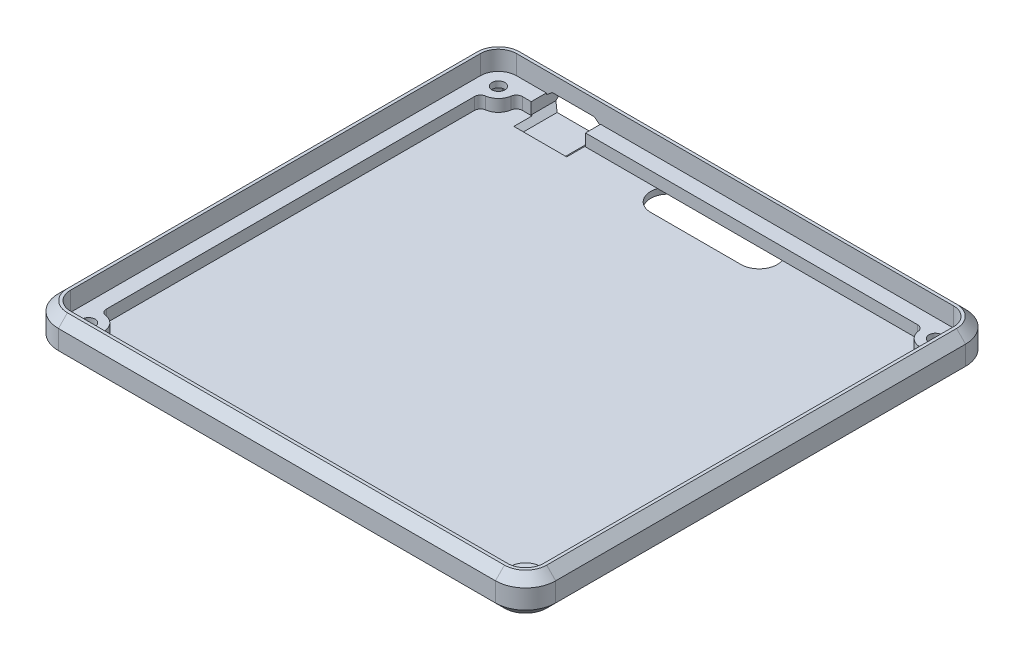
SolidWorks part; units mm, degrees
material "ABS"
ref_plane "Front Plane" through (0, 0, 0) normal (0, 0, 1) x (1, 0, 0)
ref_plane "Top Plane" through (0, 0, 0) normal (0, 1, 0) x (1, 0, 0)
ref_plane "Right Plane" through (0, 0, 0) normal (1, 0, 0) x (0, 0, -1)
sketch "Sketch2" plane through (0, 0, 0) normal (0, 1, 0) x (1, 0, 0)
  line L1 (-72.5, 74) -> (72.5, 74)
  line L2 (-78.5, 68) -> (-78.5, -68)
  line L3 (-72.5, -74) -> (72.5, -74)
  line L4 (78.5, 68) -> (78.5, -68)
  line L5 (-78.5, 74) -> (78.5, -74) construction
  line L6 (-78.5, -74) -> (78.5, 74) construction
  arc A0 (-78.5, -68) -> (-72.5, -74) centre (-72.5, -68) ccw
  arc A1 (-72.5, 74) -> (-78.5, 68) centre (-72.5, 68) ccw
  arc A2 (72.5, 74) -> (78.5, 68) centre (72.5, 68) cw
  arc A3 (72.5, -74) -> (78.5, -68) centre (72.5, -68) ccw
  point P0 (0, 0)
  dimension "D3" = 6
  dimension "D1" = 157
  dimension "D2" = 148
extrude "Boss-Extrude2" add sketch "Sketch2" along normal blind 2
sketch "Sketch3" plane through (0, 2, 0) normal (0, 1, 0) x (1, 0, 0)
  line L0 (-72.5, -74) -> (72.5, -74) construction
  line L1 (78.5, -68) -> (78.5, 68) construction
  line L2 (72.5, 74) -> (-72.5, 74) construction
  line L3 (-78.5, 68) -> (-78.5, -68) construction
  line L4 (-72.5, -74) -> (72.5, -74)
  line L5 (78.5, -68) -> (78.5, 68)
  line L6 (72.5, 74) -> (-72.5, 74)
  line L7 (-78.5, 68) -> (-78.5, -68)
  line L8 (0, -80.5945) -> (0, 82.9206) construction
  line L9 (9.041, 0) -> (-113.0904, 0) construction
  line L10 (-82.5, 68) -> (-82.5, -68)
  line L11 (-72.5, -78) -> (72.5, -78)
  line L12 (82.5, -68) -> (82.5, 68)
  line L13 (72.5, 78) -> (-72.5, 78)
  line L14 (-73.5, 63) -> (-73.5, -63)
  line L15 (-67.5, -69) -> (67.5, -69)
  line L16 (73.5, -63) -> (73.5, 63)
  line L17 (67.5, 69) -> (-67.5, 69)
  line L18 (-73.5, 63) -> (-72.5, 63)
  line L19 (-67.5, 69) -> (-67.5, 68)
  line L20 (-73.5, 68) -> (-73.5, -68) construction
  line L21 (72.5, 69) -> (-72.5, 69) construction
  line L22 (67.5, 69) -> (67.5, 68)
  line L23 (73.5, 63) -> (72.5, 63)
  line L24 (67.5, -69) -> (67.5, -68)
  line L25 (73.5, -63) -> (72.5, -63)
  line L26 (-67.5, -69) -> (-67.5, -68)
  line L27 (-73.5, -63) -> (-72.5, -63)
  line L28 (-72.5, -69) -> (72.5, -69) construction
  line L29 (73.5, -68) -> (73.5, 68) construction
  arc A0 (-78.5, -68) -> (-72.5, -74) centre (-72.5, -68) ccw construction
  arc A1 (72.5, -74) -> (78.5, -68) centre (72.5, -68) ccw construction
  arc A2 (78.5, 68) -> (72.5, 74) centre (72.5, 68) ccw construction
  arc A3 (-72.5, 74) -> (-78.5, 68) centre (-72.5, 68) ccw construction
  arc A4 (-78.5, -68) -> (-72.5, -74) centre (-72.5, -68) ccw
  arc A5 (72.5, -74) -> (78.5, -68) centre (72.5, -68) ccw
  arc A6 (78.5, 68) -> (72.5, 74) centre (72.5, 68) ccw
  arc A7 (-72.5, 74) -> (-78.5, 68) centre (-72.5, 68) ccw
  circle A9 centre (-72.5, -68) radius 2.15
  circle A10 centre (72.5, -68) radius 2.15
  circle A11 centre (72.5, 68) radius 2.15
  circle A12 centre (-72.5, 68) radius 2.15
  arc A13 (-82.5, -68) -> (-72.5, -78) centre (-72.5, -68) ccw
  arc A14 (72.5, -78) -> (82.5, -68) centre (72.5, -68) ccw
  arc A15 (82.5, 68) -> (72.5, 78) centre (72.5, 68) ccw
  arc A16 (-72.5, 78) -> (-82.5, 68) centre (-72.5, 68) ccw
  arc A21 (-72.5, 63) -> (-67.5, 68) centre (-72.5, 68) ccw
  arc A22 (72.5, 63) -> (67.5, 68) centre (72.5, 68) cw
  arc A23 (-72.5, 69) -> (-73.5, 68) centre (-72.5, 68) ccw construction
  arc A24 (72.5, -63) -> (67.5, -68) centre (72.5, -68) ccw
  arc A25 (-72.5, -63) -> (-67.5, -68) centre (-72.5, -68) cw
  arc A26 (-73.5, -68) -> (-72.5, -69) centre (-72.5, -68) ccw construction
  arc A27 (72.5, -69) -> (73.5, -68) centre (72.5, -68) ccw construction
  arc A28 (73.5, 68) -> (72.5, 69) centre (72.5, 68) ccw construction
  arc M10 (-78.5, -68) -> (-72.5, -74) centre (-72.5, -68) ccw
  line M11 (-72.5, -74) -> (72.5, -74)
  arc M12 (72.5, -74) -> (78.5, -68) centre (72.5, -68) ccw
  line M13 (78.5, -68) -> (78.5, 68)
  arc M14 (78.5, 68) -> (72.5, 74) centre (72.5, 68) ccw
  line M15 (72.5, 74) -> (-72.5, 74)
  arc M16 (-72.5, 74) -> (-78.5, 68) centre (-72.5, 68) ccw
  line M17 (-78.5, 68) -> (-78.5, -68)
  dimension "D1" = 68
  dimension "D2" = 4.3
  dimension "D3" = 72.5
  dimension "D4" = 4
  dimension "D6" = 1
  dimension "D7" = 5
  dimension "D8" = 1
  dimension "D9" = 5
  dimension "D5" = 5
extrude "Boss-Extrude3" add sketch "Sketch3" along normal blind 4 and the other way blind 2 contours L13 A16 L10 A13 L11 A14 L12 A15 M10 M17 M16 M15 M14 M13 M12 M11 | L17 L16 L15 L14 M17 M10 M11 M12 M13 M14 M15 M16 region at (-75.217, 2, 70.717) region at (-77.9654, 2, -73.4654)
sketch "Sketch8" plane through (0, 6, 0) normal (0, 1, 0) x (1, 0, 0)
  line L0 (-72.5, -78) -> (72.5, -78) construction
  line L1 (82.5, -68) -> (82.5, 68) construction
  line L2 (72.5, 78) -> (-72.5, 78) construction
  line L3 (-82.5, 68) -> (-82.5, -68) construction
  line L4 (78.5, -68) -> (78.5, 68)
  line L5 (72.5, 74) -> (-72.5, 74)
  line L6 (-78.5, 68) -> (-78.5, -68)
  line L7 (-72.5, -74) -> (72.5, -74)
  line L8 (78.5, -68) -> (78.5, 68)
  line L9 (72.5, 74) -> (-72.5, 74)
  line L10 (-78.5, 68) -> (-78.5, -68)
  line L11 (-72.5, -74) -> (72.5, -74)
  line L12 (-72.5, -78) -> (72.5, -78)
  line L13 (82.5, -68) -> (82.5, 68)
  line L14 (72.5, 78) -> (-72.5, 78)
  line L15 (-82.5, 68) -> (-82.5, -68)
  line L16 (-77.5, 68) -> (-77.5, -68)
  line L17 (-72.5, -73) -> (72.5, -73)
  line L18 (77.5, -68) -> (77.5, 68)
  line L19 (72.5, 73) -> (-72.5, 73)
  arc A0 (-82.5, -68) -> (-72.5, -78) centre (-72.5, -68) ccw construction
  arc A1 (72.5, -78) -> (82.5, -68) centre (72.5, -68) ccw construction
  arc A2 (82.5, 68) -> (72.5, 78) centre (72.5, 68) ccw construction
  arc A3 (-72.5, 78) -> (-82.5, 68) centre (-72.5, 68) ccw construction
  arc A4 (78.5, 68) -> (72.5, 74) centre (72.5, 68) ccw
  arc A5 (-72.5, 74) -> (-78.5, 68) centre (-72.5, 68) ccw
  arc A6 (-78.5, -68) -> (-72.5, -74) centre (-72.5, -68) ccw
  arc A7 (72.5, -74) -> (78.5, -68) centre (72.5, -68) ccw
  arc A8 (78.5, 68) -> (72.5, 74) centre (72.5, 68) ccw
  arc A9 (-72.5, 74) -> (-78.5, 68) centre (-72.5, 68) ccw
  arc A10 (-78.5, -68) -> (-72.5, -74) centre (-72.5, -68) ccw
  arc A11 (72.5, -74) -> (78.5, -68) centre (72.5, -68) ccw
  arc A12 (-82.5, -68) -> (-72.5, -78) centre (-72.5, -68) ccw
  arc A13 (72.5, -78) -> (82.5, -68) centre (72.5, -68) ccw
  arc A14 (82.5, 68) -> (72.5, 78) centre (72.5, 68) ccw
  arc A15 (-72.5, 78) -> (-82.5, 68) centre (-72.5, 68) ccw
  arc A16 (-77.5, -68) -> (-72.5, -73) centre (-72.5, -68) ccw
  arc A17 (72.5, -73) -> (77.5, -68) centre (72.5, -68) ccw
  arc A18 (77.5, 68) -> (72.5, 73) centre (72.5, 68) ccw
  arc A19 (-72.5, 73) -> (-77.5, 68) centre (-72.5, 68) ccw
  line M17 (72.5, 78) -> (-72.5, 78)
  arc M18 (-72.5, 78) -> (-82.5, 68) centre (-72.5, 68) ccw
  line M19 (-82.5, 68) -> (-82.5, -68)
  arc M20 (-82.5, -68) -> (-72.5, -78) centre (-72.5, -68) ccw
  line M21 (-72.5, -78) -> (72.5, -78)
  arc M22 (72.5, -78) -> (82.5, -68) centre (72.5, -68) ccw
  line M23 (82.5, -68) -> (82.5, 68)
  arc M24 (82.5, 68) -> (72.5, 78) centre (72.5, 68) ccw
  dimension "D1" = 0
  dimension "D2" = 5
extrude "Boss-Extrude4" add sketch "Sketch8" along normal blind 6.38 contours A11 L11 A10 L10 A9 L9 A8 L8 M24 M17 M18 M19 M20 M21 M22 M23 region at (-77.9654, 6, 73.4654)
sketch "Sketch9" plane through (0, 0, -78) normal (0, 0, -1) x (-1, 0, 0)
  line L0 (82.5, 0) -> (82.5, 12.38) construction
  line L7 (60.62, 7.11) -> (46.62, 7.11)
  line L8 (46.62, 7.11) -> (44.62, 5.51)
  line L14 (62.62, 5.51) -> (60.62, 7.11)
  line L15 (54.9775, 3.85) -> (29.0731, 3.85) construction
  line L16 (44.62, 5.51) -> (44.62, 2.19)
  line L17 (62.62, 5.51) -> (62.62, 2.19)
  line L18 (53.62, 7.11) -> (53.62, 5.8424) construction
  line L19 (-72.5, 0) -> (72.5, 0) construction
  line L20 (62.62, 2.19) -> (60.62, 0.59)
  line L21 (60.62, 0.59) -> (46.62, 0.59)
  line L22 (46.62, 0.59) -> (44.62, 2.19)
  point P7 (62.62, 3.85)
  point P20 (44.62, 3.85)
  dimension "D2" = 3.85
  dimension "D1" = 28.88
  dimension "D5" = 3.26
  dimension "D6" = 1.66
  dimension "D7" = 18
  dimension "D8" = 14
extrude "Cut-Extrude1" cut sketch "Sketch9" against normal blind 15
fillet "Fillet1" radius 2 8 edges at (-67.5, 4, -69) (-73.5, 4, -63) (-73.5, 4, 63) (-67.5, 4, 69) (73.5, 4, 63) (67.5, 4, 69) (67.5, 4, -69) (73.5, 4, -63)
sketch "Sketch11" plane through (0, 2, 0) normal (0, 1, 0) x (1, 0, 0)
  circle A0 centre (-72.5, 68) radius 2.15
  circle A1 centre (72.5, 68) radius 2.15
  circle A2 centre (72.5, -68) radius 2.15
  circle A3 centre (-72.5, -68) radius 2.15
  dimension "D1" = 4.3
  dimension "D2" = 4.3
  dimension "D3" = 4.3
  dimension "D4" = 4.3
extrude "Cut-Extrude3" cut sketch "Sketch11" against normal through all both and the other way through all contours A3 | A2 | A1 | A0 region at (-72.5, 2, -68) region at (72.5, 2, -68) region at (72.5, 2, 68) region at (-72.5, 2, 68)
sketch "Sketch10" plane through (0, 0, 0) normal (0, -1, 0) x (1, 0, 0)
  line L0 (0, -78) -> (0, 105.632) construction
  line L1 (72.5, -78) -> (-72.5, -78) construction
  line L2 (-82.5, 0) -> (91.4068, 0) construction
  line L3 (-82.5, -68) -> (-82.5, 68) construction
  line L4 (70.4793, 64.5) -> (68.4585, 68)
  line L5 (-68.4585, 68) -> (-70.4793, 71.5)
  line L6 (-70.4793, 71.5) -> (-74.5207, 71.5)
  line L7 (-74.5207, 71.5) -> (-76.5415, 68)
  line L8 (-76.5415, 68) -> (-74.5207, 64.5)
  line L9 (-74.5207, 64.5) -> (-70.4793, 64.5)
  line L10 (-70.4793, 64.5) -> (-68.4585, 68)
  line L11 (74.5207, 64.5) -> (70.4793, 64.5)
  line L12 (76.5415, 68) -> (74.5207, 64.5)
  line L13 (74.5207, 71.5) -> (76.5415, 68)
  line L14 (70.4793, 71.5) -> (74.5207, 71.5)
  line L15 (68.4585, 68) -> (70.4793, 71.5)
  line L16 (74.5207, -64.5) -> (70.4793, -64.5)
  line L17 (76.5415, -68) -> (74.5207, -64.5)
  line L18 (74.5207, -71.5) -> (76.5415, -68)
  line L19 (70.4793, -71.5) -> (74.5207, -71.5)
  line L20 (68.4585, -68) -> (70.4793, -71.5)
  line L21 (70.4793, -64.5) -> (68.4585, -68)
  line L22 (-70.4793, -64.5) -> (-68.4585, -68)
  line L23 (-74.5207, -64.5) -> (-70.4793, -64.5)
  line L24 (-76.5415, -68) -> (-74.5207, -64.5)
  line L25 (-74.5207, -71.5) -> (-76.5415, -68)
  line L26 (-70.4793, -71.5) -> (-74.5207, -71.5)
  line L27 (-68.4585, -68) -> (-70.4793, -71.5)
  line L28 (-72.5, 68) -> (-62.8389, 68)
  circle A0 centre (-72.5, 68) radius 3.5 construction
  circle A1 centre (-72.5, 68) radius 2.15 construction
  dimension "D3" = 7
extrude "Cut-Extrude2" cut sketch "Sketch10" against normal blind 4 contours L9 L10 L5 L6 L7 L8 | L12 L11 L4 L15 L14 L13 | L22 L27 L26 L25 L24 L23 | L17 L16 L21 L20 L19 L18 region at (-69.5615, 0, 66.3035)
chamfer "Chamfer1" distance 3 angle 45 16 edges at (-79.5711, 12.38, 75.0711) (0, 12.38, 78) (79.5711, 12.38, 75.0711) (82.5, 12.38, 0) (79.5711, 12.38, -75.0711) (0, 12.38, -78) (-82.5, 12.38, 0) (-79.5711, 12.38, -75.0711) (-79.5711, 0, -75.0711) (-82.5, 0, 0) (-79.5711, 0, 75.0711) (0, 0, 78) (79.5711, 0, 75.0711) (82.5, 0, 0) (79.5711, 0, -75.0711) (0, 0, -78)
sketch "Sketch13" plane through (0, 6, 0) normal (0, 1, 0) x (1, 0, 0)
  line L0 (-53.62, 63) -> (-53.62, 80.4308) construction
  line L1 (-46.62, 63) -> (-60.62, 63) construction
  line L2 (-44.62, 69) -> (-62.62, 69)
  line L3 (65.5718, 69) -> (-45.2325, 69) construction
  line L4 (-62.0075, 69) -> (-65.5718, 69) construction
  line L5 (-62.62, 69) -> (-62.62, 74)
  line L6 (-62.0075, 74) -> (-72.5, 74) construction
  line L7 (-62.62, 74) -> (-44.62, 74)
  line L8 (72.5, 74) -> (-72.5, 74) construction
  line L9 (-44.62, 74) -> (-44.62, 69)
  dimension "D1" = 9
  dimension "D2" = 9
extrude "Cut-Extrude5" cut sketch "Sketch13" against normal blind 1
sketch "Sketch14" plane through (0, 0, 0) normal (0, -1, 0) x (1, 0, 0)
  line L0 (0, 15.7154) -> (0, -85.3561) construction
  line L1 (-72.5, -75) -> (72.5, -75) construction
  circle A0 centre (-50, -50) radius 10
  circle A1 centre (50, -50) radius 10
  dimension "D1" = 20
  dimension "D2" = 50
  dimension "D3" = 25
extrude "Cut-Extrude6" cut sketch "Sketch14" against normal blind 1
sketch "Sketch15" plane through (0, 0, 0) normal (0, -1, 0) x (1, 0, 0)
  line L0 (0, 10.9905) -> (0, -88.4375) construction
  line L1 (-15, -67) -> (15, -67) construction
  line L2 (-15, -61) -> (15, -61)
  line L3 (-15, -73) -> (15, -73)
  line L4 (-72.5, -75) -> (72.5, -75) construction
  arc A0 (-15, -61) -> (-15, -73) centre (-15, -67) ccw
  arc A1 (15, -73) -> (15, -61) centre (15, -67) ccw
  point P5 (0, -67)
  dimension "D1" = 8
  dimension "D2" = 12
  dimension "D3" = 30
extrude "Cut-Extrude7" cut sketch "Sketch15" against normal blind 2
